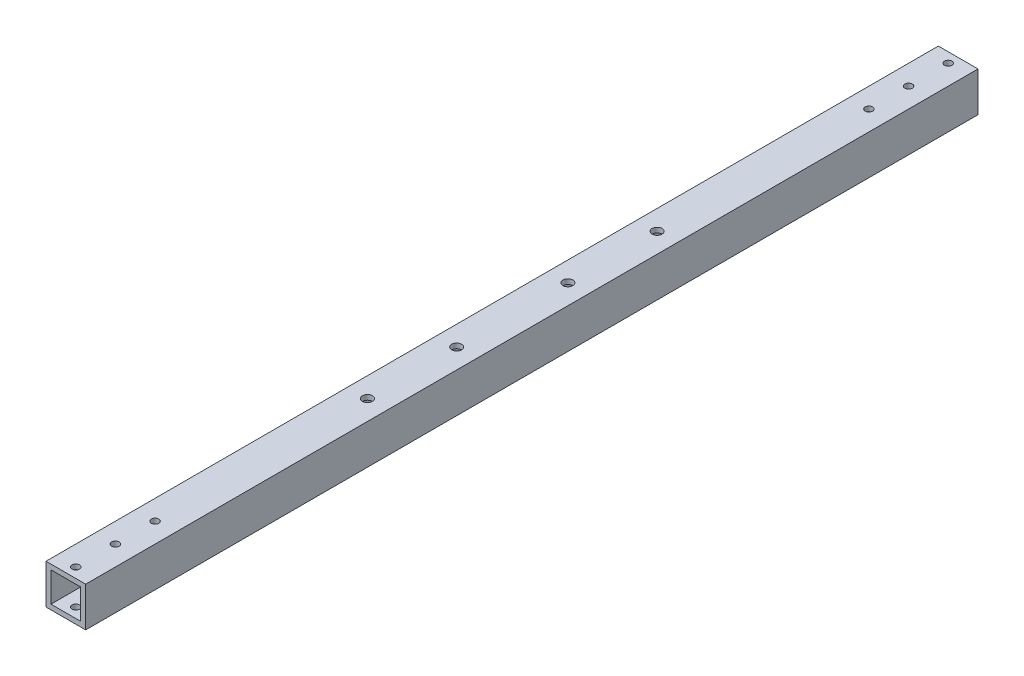
SolidWorks part; units mm, degrees
material "6061-T6 (SS)"
ref_plane "Front Plane" through (0, 0, 0) normal (0, 0, 1) x (1, 0, 0)
ref_plane "Top Plane" through (0, 0, 0) normal (0, 1, 0) x (1, 0, 0)
ref_plane "Right Plane" through (0, 0, 0) normal (1, 0, 0) x (0, 0, -1)
sketch "Sketch1" plane through (0, 0, 0) normal (0, 0, 1) x (1, 0, 0)
  line L1 (-12.7, -12.7) -> (12.7, -12.7)
  line L2 (-12.7, -12.7) -> (-12.7, 12.7)
  line L3 (-12.7, 12.7) -> (12.7, 12.7)
  line L4 (12.7, -12.7) -> (12.7, 12.7)
  line L5 (-12.7, -12.7) -> (12.7, 12.7) construction
  line L6 (-12.7, 12.7) -> (12.7, -12.7) construction
  point P0 (0, 0)
  point P5 (0, 0)
  point P8 (0, 0)
  point P9 (0, 0)
  point P12 (0, 0)
  point P14 (0, 0)
  dimension "D1" = 25.4
  dimension "D2" = 25.4
extrude "Extrude-Thin1" add sketch "Sketch1" along normal blind 571.5 thin thin type one direction reverse wall 3.175
hole_wizard "3/16 (0.1875) Diameter Hole1" positions "3DSketch1" profile "Sketch3" hole size "3/16" standard "ANSI Inch" end condition through all
sketch3d "3DSketch1"
  line L1 (12.7, 12.7, 0) -> (-12.7, 12.7, 0) construction
  line L6 (0, 12.7, 571.5) -> (0, 12.7, 0) construction
  line L7 (12.7, 12.7, 571.5) -> (-12.7, 12.7, 571.5) construction
  point P57 (0, 12.7, 6.35)
  point P59 (0, 12.7, 31.75)
  point P61 (0, 12.7, 57.15)
  point P63 (0, 12.7, 539.75)
  point P65 (0, 12.7, 514.35)
  point P67 (0, 12.7, 565.15)
  dimension "D1" = 25.4
  dimension "D2" = 25.4
  dimension "D3" = 6.35
  dimension "D4" = 25.4
  dimension "D5" = 25.4
  dimension "D6" = 6.35
sketch "Sketch3" plane through (0, 12.7, 565.15) normal (1, 0, 0) x (0, 0, 1)
  line L0 (0, 0) -> (0, 25.4)
  line L1 (0, 25.4) -> (2.3812, 25.4)
  line L2 (2.3812, 25.4) -> (2.3812, 0)
  line L5 (2.3812, 0) -> (0, 0)
  line L11 (0, -6.35) -> (0, 107.95) construction
  dimension "Thru Hole Dia." = 4.7625
  dimension "Thru Hole Depth" = 25.4
hole_wizard "1/4 (0.25) Diameter Hole1" positions "Sketch6" profile "Sketch7" hole size "1/4" standard "ANSI Inch" end condition through all
sketch "Sketch6" plane through (0, 12.7, 0) normal (0, 1, 0) x (1, 0, 0)
  point P0 (0, -321.183)
  point P3 (0, -378.333)
  point P6 (0, -192.786)
  point P9 (0, -249.936)
sketch "Sketch7" plane through (0, 12.7, 321.183) normal (1, 0, 0) x (0, 0, 1)
  line L0 (0, 0) -> (0, 25.4)
  line L1 (0, 25.4) -> (3.175, 25.4)
  line L2 (3.175, 25.4) -> (3.175, 0)
  line L5 (3.175, 0) -> (0, 0)
  line L11 (0, -6.35) -> (0, 107.95) construction
  dimension "Thru Hole Dia." = 6.35
  dimension "Thru Hole Depth" = 25.4
